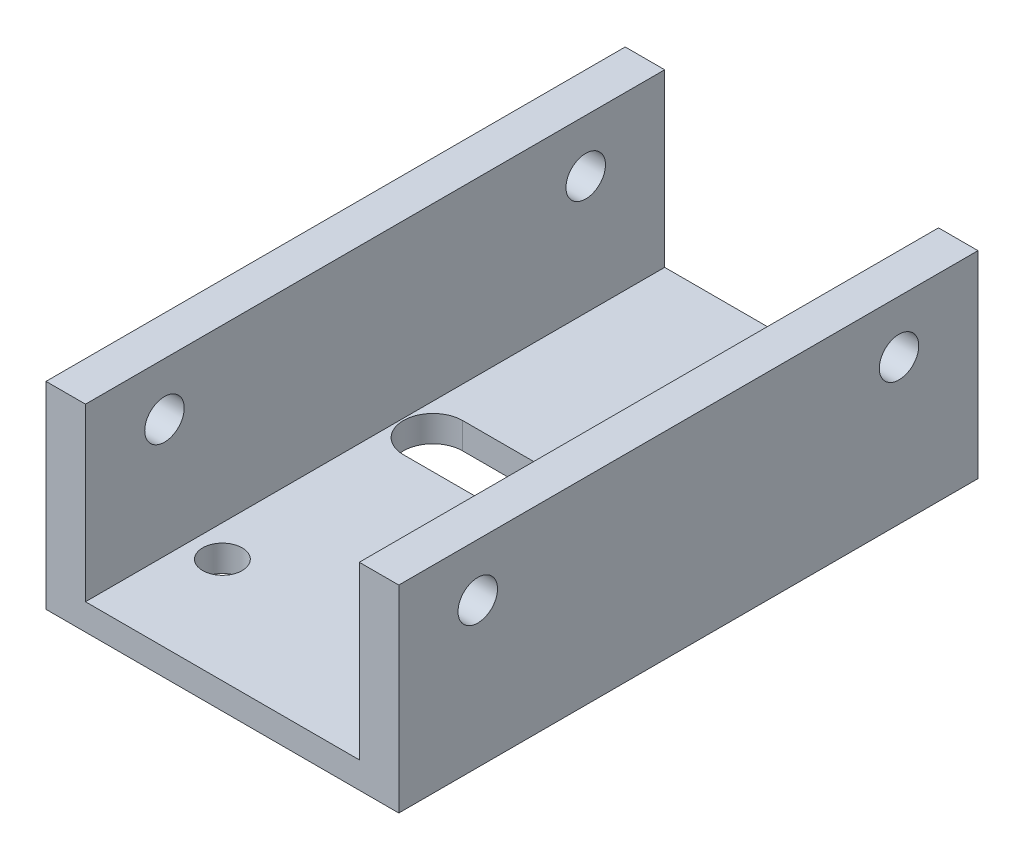
SolidWorks part; units mm, degrees
ref_plane "Front Plane" through (0, 0, 0) normal (0, 0, 1) x (1, 0, 0)
ref_plane "Top Plane" through (0, 0, 0) normal (0, 1, 0) x (1, 0, 0)
ref_plane "Right Plane" through (0, 0, 0) normal (1, 0, 0) x (0, 0, -1)
sketch "Sketch2" plane through (0, 0, 0) normal (0, 0, 1) x (1, 0, 0)
  line L0 (23.8, 15) -> (26.8, 15)
  line L1 (0, 0) -> (26.8, 0)
  line L2 (0, 0) -> (0, 15)
  line L3 (0, 15) -> (3, 15)
  line L4 (26.8, 0) -> (26.8, 15)
  line L6 (3, 15) -> (3, 2)
  line L7 (3, 2) -> (23.8, 2)
  line L8 (23.8, 15) -> (23.8, 2)
  dimension "D1" = 3
  dimension "D2" = 15
  dimension "D3" = 2
  dimension "D4" = 26.8
extrude "Boss-Extrude1" add sketch "Sketch2" along normal blind 44
fillet "Fillet1" [suppressed] radius 2
sketch "Sketch3" plane through (0, 0, 0) normal (0, -1, 0) x (1, 0, 0)
  line L1 (0, 0) -> (26.8, 0) construction
  line L3 (3, 44) -> (3, 0) construction
  line L4 (23.8, 44) -> (23.8, 0) construction
  line L6 (21.4, 17.75) -> (5.4, 17.75)
  line L7 (21.4, 22.25) -> (5.4, 22.25)
  circle A0 centre (21.4, 36) radius 1.5
  circle A1 centre (13.4, 8) radius 1.5
  circle A2 centre (5.4, 36) radius 1.5
  arc A3 (5.4, 22.25) -> (5.4, 17.75) centre (5.4, 20) ccw
  arc A4 (21.4, 17.75) -> (21.4, 22.25) centre (21.4, 20) ccw
  dimension "D1" = 3
  dimension "D7" = 4.5
  dimension "D2" = 16
  dimension "D3" = 8
  dimension "D4" = 2.4
  dimension "D5" = 2.4
  dimension "D6" = 16
extrude "Cut-Extrude1" cut sketch "Sketch3" against normal blind 30
sketch "Sketch4" plane through (0, 0, 0) normal (-1, 0, 0) x (0, 0, 1)
  line L0 (44, 15) -> (0, 15) construction
  line L1 (0, 15) -> (0, 0) construction
  line L2 (44, 15) -> (44, 0) construction
  circle A0 centre (6, 11) radius 1.5
  circle A1 centre (38, 11) radius 1.5
  dimension "D1" = 3
  dimension "D4" = 6
  dimension "D5" = 6
  dimension "D2" = 4
  dimension "D3" = 4
extrude "Cut-Extrude2" cut sketch "Sketch4" against normal blind 30
